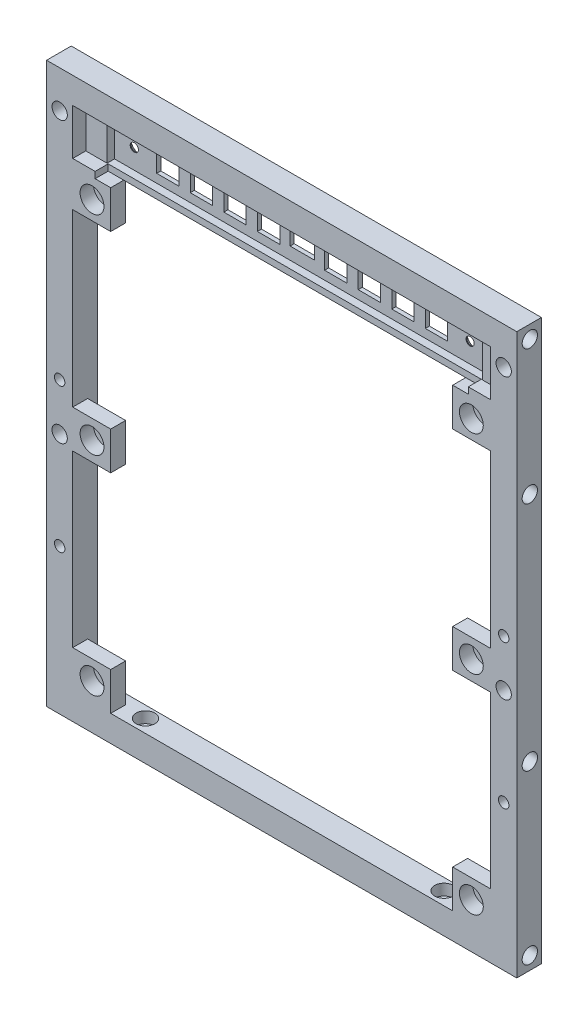
SolidWorks part; units mm, degrees
ref_plane "Front Plane" through (0, 0, 0) normal (0, 0, 1) x (1, 0, 0)
ref_plane "Top Plane" through (0, 0, 0) normal (0, 1, 0) x (1, 0, 0)
ref_plane "Right Plane" through (0, 0, 0) normal (1, 0, 0) x (0, 0, -1)
sketch "Sketch1" plane through (0, 0, 0) normal (0, 0, 1) x (1, 0, 0)
  line L1 (-63, -75) -> (63, -75)
  line L2 (-63, -75) -> (-63, 75)
  line L3 (-63, 75) -> (63, 75)
  line L4 (63, -75) -> (63, 75)
  line L5 (-63, -75) -> (63, 75) construction
  line L6 (-63, 75) -> (63, -75) construction
  line L7 (-56, -68) -> (56, -68)
  line L8 (-56, -68) -> (-56, 68)
  line L9 (-56, 68) -> (56, 68)
  line L10 (56, -68) -> (56, 68)
  line L11 (-56, -68) -> (56, 68) construction
  line L12 (-56, 68) -> (56, -68) construction
  point P0 (0, 0)
  point P6 (0, 0)
  dimension "D1" = 126
  dimension "D2" = 150
  dimension "D3" = 7
  dimension "D4" = 7
extrude "Boss-Extrude1" add sketch "Sketch1" along normal blind 7
sketch "Sketch2" plane through (-63, 0, 0) normal (-1, 0, 0) x (0, 0, 1)
  line L0 (3.5, 71.5) -> (3.5, -71.5) construction
  line L1 (7, 75) -> (0, 75) construction
  circle A0 centre (3.5, -71.5) radius 2.05
  circle A2 centre (3.5, 71.5) radius 2.05
  circle A3 centre (3.5, 35.5) radius 2.05
  circle A4 centre (3.5, -26.5) radius 2.05
  point P2 (3.5, 0)
  point P7 (3.5, 75)
  dimension "D2" = 4.1
  dimension "D3" = 36
  dimension "D4" = 45
  dimension "D1" = 3.5
extrude "Cut-Extrude1" cut sketch "Sketch2" against normal blind 6
mirror "Mirror1" about plane through (0, 0, 0) normal (1, 0, 0) of "Cut-Extrude1"
sketch "Sketch3" plane through (0, -68, 0) normal (0, 1, 0) x (1, 0, 0)
  line L0 (0, 0) -> (0, -7) construction
  line L1 (-56, 0) -> (56, 0) construction
  line L2 (-56, -7) -> (56, -7) construction
  line L3 (40, -3.5) -> (-40, -3.5) construction
  circle A0 centre (40, -3.5) radius 1.35
  circle A1 centre (-40, -3.5) radius 1.35
  point P9 (0, -3.5)
  dimension "D1" = 2.7
  dimension "D2" = 80
extrude "Cut-Extrude2" cut sketch "Sketch3" against normal through all
sketch "Sketch4" plane through (0, -68, 0) normal (0, 1, 0) x (1, 0, 0)
  circle A0 centre (40, -3.5) radius 2.5
  circle A1 centre (-40, -3.5) radius 2.5
  dimension "D1" = 5
extrude "Cut-Extrude3" cut sketch "Sketch4" against normal blind 3
sketch "Sketch5" plane through (0, 0, 0) normal (0, 0, -1) x (-1, 0, 0)
  line L0 (-59.5, -75) -> (-59.5, 75) construction
  line L1 (63, -75) -> (-63, -75) construction
  line L2 (-63, 75) -> (63, 75) construction
  line L3 (-56, 0) -> (-63, 0) construction
  line L4 (-56, -68) -> (-56, 68) construction
  line L5 (-63, -75) -> (-63, 75) construction
  line L6 (0, 75) -> (0, -75) construction
  line L7 (56, -68) -> (-56, -68) construction
  circle A0 centre (-59.5, 2.6) radius 1.4
  circle A1 centre (59.5, 2.6) radius 1.4
  circle A2 centre (-59.5, -36) radius 1.4
  circle A3 centre (59.5, -36) radius 1.4
  point P12 (-59.5, 0)
  point P13 (-59.5, 0)
  dimension "D1" = 2.8
  dimension "D2" = 2.6
  dimension "D3" = 32
extrude "Cut-Extrude4" cut sketch "Sketch5" against normal through all
sketch "Sketch6" plane through (0, 0, 0) normal (0, 0, -1) x (-1, 0, 0)
  circle A0 centre (-59.5, 2.6) radius 2.5
  circle A1 centre (59.5, 2.6) radius 2.5
  circle A2 centre (-59.5, -36) radius 2.5
  circle A3 centre (59.5, -36) radius 2.5
  dimension "D1" = 5
extrude "Cut-Extrude5" cut sketch "Sketch6" against normal blind 3
sketch "Sketch7" plane through (0, 0, 0) normal (0, 0, -1) x (-1, 0, 0)
  line L0 (-56, 68) -> (-63, 68) construction
  line L1 (-63, -75) -> (-63, 75) construction
  line L2 (-59.5, 65) -> (-59.5, -10) construction
  line L3 (-63, 75) -> (63, 75) construction
  circle A0 centre (-59.5, 65) radius 2.05
  circle A1 centre (-59.5, -10) radius 2.05
  point P8 (-59.5, 68)
  dimension "D1" = 4.1
  dimension "D2" = 10
  dimension "D3" = 75
extrude "Cut-Extrude6" cut sketch "Sketch7" against normal through all
mirror "Mirror2" about plane through (0, 0, 0) normal (1, 0, 0) of "Cut-Extrude6"
sketch "Sketch8" plane through (0, 0, 3) normal (0, 0, -1) x (-1, 0, 0)
  line L2 (-60.9, 0.5288) -> (-60.9, 4.6712)
  line L4 (-58.1, 0.5288) -> (-58.1, 4.6712)
  line L5 (-60.9, 0.5288) -> (-58.1, 4.6712) construction
  line L6 (-60.9, 4.6712) -> (-58.1, 0.5288) construction
  line L8 (-60.9, -38.0712) -> (-60.9, -33.9288)
  line L10 (-58.1, -38.0712) -> (-58.1, -33.9288)
  line L11 (-60.9, -38.0712) -> (-58.1, -33.9288) construction
  line L12 (-60.9, -33.9288) -> (-58.1, -38.0712) construction
  circle A0 centre (-59.5, 2.6) radius 2.5 construction
  circle A1 centre (-59.5, -36) radius 2.5 construction
  circle A2 centre (-59.5, -36) radius 2.5 construction
  arc A3 (-58.1, 4.6712) -> (-60.9, 4.6712) centre (-59.5, 2.6) ccw
  arc A4 (-58.1, -33.9288) -> (-60.9, -33.9288) centre (-59.5, -36) ccw
  circle A5 centre (-59.5, 2.6) radius 1.4 construction
  circle A6 centre (-59.5, -36) radius 1.4 construction
  arc A7 (-60.9, -38.0712) -> (-58.1, -38.0712) centre (-59.5, -36) ccw
  arc A8 (-60.9, 0.5288) -> (-58.1, 0.5288) centre (-59.5, 2.6) ccw
  point P0 (-59.5, 2.6)
  point P8 (-59.5, -36)
extrude "Cut-Extrude7" cut sketch "Sketch8" against normal blind 0.2
sketch "Sketch9" plane through (0, 0, 3.2) normal (0, 0, -1) x (-1, 0, 0)
  line L0 (-58.1, 2.6) -> (-58.1, 4.6712) construction
  line L1 (-60.9, 1.2) -> (-58.1, 1.2)
  line L2 (-60.9, 1.2) -> (-60.9, 4)
  line L3 (-60.9, 4) -> (-58.1, 4)
  line L4 (-58.1, 1.2) -> (-58.1, 4)
  line L5 (-60.9, 1.2) -> (-58.1, 4) construction
  line L6 (-60.9, 4) -> (-58.1, 1.2) construction
  line L7 (-58.1, -38.0712) -> (-58.1, -33.9288) construction
  line L8 (-60.9, -37.4) -> (-58.1, -37.4)
  line L9 (-60.9, -37.4) -> (-60.9, -34.6)
  line L10 (-60.9, -34.6) -> (-58.1, -34.6)
  line L11 (-58.1, -37.4) -> (-58.1, -34.6)
  line L12 (-60.9, -37.4) -> (-58.1, -34.6) construction
  line L13 (-60.9, -34.6) -> (-58.1, -37.4) construction
  arc A0 (-58.1, 2.6) -> (-60.9, 2.6) centre (-59.5, 2.6) ccw construction
  point P0 (-59.5, 2.6)
  point P8 (-59.5, -36)
extrude "Cut-Extrude8" cut sketch "Sketch9" against normal blind 0.2
mirror "Mirror3" about plane through (0, 0, 0) normal (1, 0, 0) of "Cut-Extrude8", "Cut-Extrude7"
sketch "Sketch10" plane through (0, 0, 7) normal (0, 0, 1) x (1, 0, 0)
  line L0 (56, -68) -> (56, 68) construction
  line L1 (56, -68) -> (50, -68)
  line L2 (56, -68) -> (56, -62)
  line L3 (56, -62) -> (50, -62)
  line L4 (50, -68) -> (50, -62)
  line L5 (56, -38.5) -> (50, -38.5)
  line L6 (56, -38.5) -> (56, -32.5)
  line L7 (56, -32.5) -> (50, -32.5)
  line L8 (50, -38.5) -> (50, -32.5)
  line L9 (-56, -68) -> (56, -68) construction
  dimension "D1" = 6
  dimension "D2" = 35.5
extrude "Boss-Extrude2" add sketch "Sketch10" against normal offset from surface (5.5 mm away) 1.5 up to face at (-57.45, -10, 0)
sketch "Sketch11" plane through (0, 0, 1.5) normal (0, 0, -1) x (-1, 0, 0)
  line L0 (-56, -38.5) -> (-50, -32.5) construction
  line L2 (-56, -68) -> (-50, -62) construction
  circle A0 centre (-53, -35.5) radius 1.65
  circle A1 centre (-53, -65) radius 1.65
  dimension "D1" = 3.3
extrude "Cut-Extrude9" cut sketch "Sketch11" against normal through all
mirror "Mirror4" about plane through (0, 0, 0) normal (1, 0, 0) of "Cut-Extrude9", "Boss-Extrude2"
sketch "Sketch12" plane through (0, 0, 0) normal (0, 0, -1) x (-1, 0, 0)
  line L0 (56, 68) -> (56, -68) construction
  line L1 (-56, 68) -> (56, 68)
  line L2 (-56, 68) -> (-56, 54)
  line L3 (-56, 54) -> (56, 54)
  line L4 (56, 68) -> (56, 54)
  dimension "D1" = 14
extrude "Boss-Extrude3" add sketch "Sketch12" against normal blind 1.5
sketch "Sketch13" plane through (0, 0, 1.5) normal (0, 0, 1) x (1, 0, 0)
  line L0 (-56, 68) -> (56, 54) construction
  line L2 (-50.3, 55.7) -> (50.3, 55.7)
  line L3 (-50.3, 55.7) -> (-50.3, 66.3)
  line L4 (-50.3, 66.3) -> (50.3, 66.3)
  line L5 (50.3, 55.7) -> (50.3, 66.3)
  line L6 (-50.3, 55.7) -> (50.3, 66.3) construction
  line L7 (-50.3, 66.3) -> (50.3, 55.7) construction
  line L8 (-56, 54) -> (56, 54)
  line L9 (-56, 54) -> (-56, 68)
  line L10 (-56, 68) -> (56, 68)
  line L11 (56, 54) -> (56, 68)
  line L12 (-56, 54) -> (56, 68) construction
  line L13 (-56, 68) -> (56, 54) construction
  point P4 (0, 61)
  point P9 (0, 61)
  dimension "D1" = 100.6
  dimension "D2" = 10.6
extrude "Boss-Extrude4" add sketch "Sketch13" along normal blind 2
sketch "Sketch14" plane through (0, 0, 1.5) normal (0, 0, 1) x (1, 0, 0)
  line L0 (0, 66.3) -> (0, 55.7) construction
  line L1 (50.3, 66.3) -> (-50.3, 66.3) construction
  line L2 (-50.3, 55.7) -> (50.3, 55.7) construction
  line L3 (-50.3, 61) -> (50.3, 61) construction
  line L4 (50.3, 55.7) -> (50.3, 66.3) construction
  line L5 (-33, 64) -> (-39, 64)
  line L6 (-3.25, 59) -> (3.25, 59)
  line L7 (-3.25, 59) -> (-3.25, 63)
  line L8 (-3.25, 63) -> (3.25, 63)
  line L9 (3.25, 59) -> (3.25, 63)
  line L10 (-3.25, 59) -> (3.25, 63) construction
  line L11 (-3.25, 63) -> (3.25, 59) construction
  line L12 (6, 58) -> (12, 58)
  line L13 (6, 58) -> (6, 64)
  line L14 (6, 64) -> (12, 64)
  line L15 (12, 58) -> (12, 64)
  line L16 (6, 58) -> (12, 64) construction
  line L17 (6, 64) -> (12, 58) construction
  line L18 (15, 58) -> (21, 58)
  line L19 (15, 58) -> (15, 64)
  line L20 (15, 64) -> (21, 64)
  line L21 (21, 58) -> (21, 64)
  line L22 (15, 58) -> (21, 64) construction
  line L23 (15, 64) -> (21, 58) construction
  line L24 (24, 58) -> (30, 58)
  line L25 (24, 58) -> (24, 64)
  line L26 (24, 64) -> (30, 64)
  line L27 (30, 58) -> (30, 64)
  line L28 (24, 58) -> (30, 64) construction
  line L29 (24, 64) -> (30, 58) construction
  line L30 (33, 58) -> (39, 58)
  line L31 (33, 58) -> (33, 64)
  line L32 (33, 64) -> (39, 64)
  line L33 (39, 58) -> (39, 64)
  line L34 (33, 58) -> (39, 64) construction
  line L35 (33, 64) -> (39, 58) construction
  line L36 (-39, 58) -> (-39, 64)
  line L37 (-33, 58) -> (-39, 58)
  line L38 (-33, 58) -> (-33, 64)
  line L39 (-24, 64) -> (-30, 64)
  line L40 (-30, 58) -> (-30, 64)
  line L41 (-24, 58) -> (-30, 58)
  line L42 (-24, 58) -> (-24, 64)
  line L43 (-15, 64) -> (-21, 64)
  line L44 (-21, 58) -> (-21, 64)
  line L45 (-15, 58) -> (-21, 58)
  line L46 (-15, 58) -> (-15, 64)
  line L47 (-6, 64) -> (-12, 64)
  line L48 (-12, 58) -> (-12, 64)
  line L49 (-6, 58) -> (-12, 58)
  line L50 (-6, 58) -> (-6, 64)
  circle A0 centre (-45, 61) radius 1.3 construction
  circle A1 centre (45, 61) radius 1.3 construction
  point P6 (0, 61)
  point P11 (0, 61)
  point P16 (9, 61)
  point P21 (18, 61)
  point P26 (27, 61)
  point P31 (36, 61)
  dimension "D10" = 2.6
  dimension "D9" = 45
  dimension "D1" = 6.5
  dimension "D2" = 4
  dimension "D3" = 6
  dimension "D4" = 9
  dimension "D5" = 9
  dimension "D6" = 9
  dimension "D7" = 9
  dimension "D8" = 45
extrude "Cut-Extrude10" cut sketch "Sketch14" against normal through all
sketch "Sketch15" plane through (0, 0, 1.5) normal (0, 0, 1) x (1, 0, 0)
  circle A0 centre (-45, 61) radius 1
  circle A1 centre (45, 61) radius 1
  dimension "D1" = 2
extrude "Boss-Extrude5" add sketch "Sketch15" along normal up to surface (2 mm away) up to face at (0, 61, 3.5)
chamfer "Chamfer1" distance 0.4 angle 45 3 edges at (-56, -7, 0) (56, -7, 0) (0, -68, 0) tangent propagation no
chamfer "Chamfer2" distance 0.4 angle 45 4 edges at (0, 75, 0) (-63, 0, 0) (0, -75, 0) (63, 0, 0)
chamfer "Chamfer3" distance 0.4 angle 45 36 edges at (-36, 58, 0) (-39, 61, 0) (-36, 64, 0) (-33, 61, 0) (-27, 58, 0) (-30, 61, 0) (-27, 64, 0) (-24, 61, 0) (-18, 58, 0) (-21, 61, 0) (-18, 64, 0) (-15, 61, 0) (-9, 58, 0) (-12, 61, 0) (-9, 64, 0) (-6, 61, 0) (0, 59, 0) (-3.25, 61, 0) (0, 63, 0) (3.25, 61, 0) (9, 58, 0) (6, 61, 0) (9, 64, 0) (12, 61, 0) (18, 58, 0) (15, 61, 0) (18, 64, 0) (21, 61, 0) (36, 58, 0) (33, 61, 0) (36, 64, 0) (39, 61, 0) (27, 58, 0) (24, 61, 0) (27, 64, 0) (30, 61, 0)
sketch "Sketch16" plane through (0, 0, 7) normal (0, 0, 1) x (1, 0, 0)
  line L0 (-50, 54) -> (-50, 55.7)
  line L1 (-56, -32.5) -> (-50, -32.5)
  line L2 (-56, -32.5) -> (-56, -26.5)
  line L3 (-56, -26.5) -> (-50, -26.5)
  line L4 (-50, -32.5) -> (-50, -26.5)
  line L5 (56, -32.5) -> (50, -32.5)
  line L6 (56, -32.5) -> (56, -26.5)
  line L7 (56, -26.5) -> (50, -26.5)
  line L8 (50, -32.5) -> (50, -26.5)
  line L9 (56, 54) -> (50, 54) construction
  line L10 (56, 54) -> (56, 48)
  line L11 (56, 48) -> (50, 48)
  line L12 (50, 54) -> (50, 48)
  line L13 (-56, 54) -> (-50, 54) construction
  line L14 (-56, 54) -> (-56, 48)
  line L15 (-56, 48) -> (-50, 48)
  line L16 (-50, 54) -> (-50, 48)
  line L17 (-50.3, 55.7) -> (50.3, 55.7) construction
  line L18 (-50, 55.7) -> (-56, 55.7)
  line L19 (-56, 68) -> (-56, 54) construction
  line L20 (-56, 55.7) -> (-56, 54)
  line L21 (50, 54) -> (50, 55.7)
  line L22 (50, 55.7) -> (56, 55.7)
  line L23 (56, 54) -> (56, 68) construction
  line L24 (56, 55.7) -> (56, 54)
  dimension "D1" = 6
extrude "Boss-Extrude7" add sketch "Sketch16" against normal offset from surface (5.5 mm away) 1.5 up to face at (-36, 61, 0)
sketch "Sketch17" plane through (0, 0, 1.5) normal (0, 0, -1) x (-1, 0, 0)
  line L0 (-50, 48) -> (50, -26.5) construction
  line L1 (-50, -26.5) -> (-50, -38.5) construction
  line L2 (-53, -29.5) -> (53, -29.5) construction
  line L3 (-53, -29.5) -> (-53, 51) construction
  line L4 (-53, 51) -> (53, 51) construction
  line L5 (53, -29.5) -> (53, 51) construction
  line L6 (-53, -29.5) -> (53, 51) construction
  line L7 (-53, 51) -> (53, -29.5) construction
  line L8 (50, -26.5) -> (56, -26.5) construction
  circle A0 centre (-53, -29.5) radius 1.65
  circle A1 centre (53, -29.5) radius 1.65
  circle A2 centre (53, 51) radius 1.65
  circle A3 centre (-53, 51) radius 1.65
  point P4 (0, 10.75)
  dimension "D3" = 3.3
  dimension "D1" = 3
  dimension "D2" = 3
extrude "Cut-Extrude11" cut sketch "Sketch17" against normal through all
sketch "Sketch18" plane through (0, 0, 1.5) normal (0, 0, 1) x (1, 0, 0)
  circle A0 centre (-45, 61) radius 1.1
  circle A1 centre (45, 61) radius 1.1
  dimension "D1" = 2.2
extrude "Cut-Extrude12" cut sketch "Sketch18" against normal through all both and the other way through all
chamfer "Chamfer4" distance 1.3 angle 45 2 edges at (-43.9, 61, 0) (46.1, 61, 0)
sketch "Sketch19" plane through (0, 0, 1.5) normal (0, 0, -1) x (-1, 0, 0)
  line L1 (-56, -68) -> (56, -68)
  line L2 (-56, -68) -> (-56, 54)
  line L3 (-56, 54) -> (56, 54)
  line L4 (56, -68) -> (56, 54)
extrude "Cut-Extrude13" cut sketch "Sketch19" against normal through all
ref_plane "Plane1" through (0, 0, 3) normal (0, 0, 1) x (1, 0, 0)
sketch "Sketch20" plane through (0, 0, 3) normal (0, 0, 1) x (1, 0, 0)
  line L0 (56, 54) -> (56, -68) construction
  line L1 (56, -68) -> (48, -68)
  line L2 (56, -68) -> (56, -60)
  line L3 (56, -60) -> (48, -60)
  line L4 (48, -68) -> (48, -60)
  line L5 (56, 54) -> (48, 54)
  line L6 (56, 54) -> (56, 46)
  line L7 (56, 46) -> (48, 46)
  line L8 (48, 54) -> (48, 46)
  line L9 (56, -24.5) -> (48, -24.5)
  line L10 (56, -24.5) -> (56, -32.5)
  line L11 (56, -32.5) -> (48, -32.5)
  line L12 (48, -24.5) -> (48, -32.5)
  dimension "D1" = 8
  dimension "D2" = 27.5
extrude "Boss-Extrude8" add sketch "Sketch20" along normal blind 7
sketch "Sketch21" plane through (0, 0, 3) normal (0, 0, -1) x (-1, 0, 0)
  line L0 (-48, 54) -> (-56, 46) construction
  line L1 (-56, -60) -> (-48, -68) construction
  line L2 (-56, -24.5) -> (-48, -32.5) construction
  circle A0 centre (-52, 50) radius 2.1
  circle A1 centre (-52, -64) radius 2.1
  circle A2 centre (-52, -28.5) radius 2.1
  dimension "D1" = 4.2
extrude "Cut-Extrude14" cut sketch "Sketch21" against normal through all
mirror "Mirror5" about plane through (0, 0, 0) normal (1, 0, 0) of "Cut-Extrude14", "Boss-Extrude8"
chamfer "Chamfer5" distance 3 angle 45 6 edges at (-56, -64, 7) (56, -64, 7) (56, 50, 7) (-56, 50, 7) (-56, -28.5, 7) (56, -28.5, 7)
sketch "Sketch22" plane through (0, 0, 3) normal (0, 0, -1) x (-1, 0, 0)
  line L1 (-56, 54) -> (56, 54)
  line L2 (-56, 54) -> (-56, -68)
  line L3 (-56, -68) -> (56, -68)
  line L4 (56, 54) -> (56, -68)
extrude "Cut-Extrude15" cut sketch "Sketch22" against normal blind 10
sketch "Sketch23" plane through (-56, 0, 0) normal (1, 0, 0) x (0, 0, -1)
  line L1 (-7, 54) -> (-10, 54)
  line L2 (-7, 54) -> (-7, -68)
  line L3 (-7, -68) -> (-10, -68)
  line L4 (-10, 54) -> (-10, -68)
extrude "Cut-Extrude16" cut sketch "Sketch23" against normal through all both and the other way through all
sketch "Sketch24" plane through (0, 0, 0) normal (0, 0, -1) x (-1, 0, 0)
  circle A0 centre (-50.825, 48.75) radius 3.2 construction
  circle A1 centre (-50.825, -62.95) radius 3.2 construction
  circle A2 centre (-50.825, -7.1) radius 3.2 construction
  circle A3 centre (50.825, -62.95) radius 3.2 construction
  circle A4 centre (50.825, -7.1) radius 3.2 construction
  circle A5 centre (50.825, 48.75) radius 3.2 construction
  circle A6 centre (-50.825, 48.75) radius 3.2
  circle A7 centre (-50.825, -62.95) radius 3.2
  circle A8 centre (-50.825, -7.1) radius 3.2
  circle A9 centre (50.825, -62.95) radius 3.2
  circle A10 centre (50.825, -7.1) radius 3.2
  circle A11 centre (50.825, 48.75) radius 3.2
sketch "Sketch25" plane through (0, 0, 3) normal (0, 0, 1) x (1, 0, 0)
  line L0 (-56, 54) -> (-56, -68) construction
  line L1 (-56, 54) -> (-45.825, 54)
  line L2 (-56, 54) -> (-56, 43.825)
  line L3 (-56, 43.825) -> (-45.825, 43.825)
  line L4 (-45.825, 54) -> (-45.825, 43.825)
  line L5 (-56, -2.0125) -> (-45.825, -2.0125)
  line L6 (-56, -2.0125) -> (-56, -12.1875)
  line L7 (-56, -12.1875) -> (-45.825, -12.1875)
  line L8 (-45.825, -2.0125) -> (-45.825, -12.1875)
  line L9 (0, 54) -> (0, -68) construction
  line L10 (-56, -68) -> (-45.825, -68)
  line L11 (-56, -68) -> (-56, -57.825)
  line L12 (-56, -57.825) -> (-45.825, -57.825)
  line L13 (-45.825, -68) -> (-45.825, -57.825)
  line L14 (-50, 54) -> (50, 54) construction
  line L15 (-56, -68) -> (56, -68) construction
  line L16 (45.825, -68) -> (45.825, -57.825)
  line L17 (56, -57.825) -> (45.825, -57.825)
  line L18 (56, -68) -> (56, -57.825)
  line L19 (56, -68) -> (45.825, -68)
  line L20 (45.825, -2.0125) -> (45.825, -12.1875)
  line L21 (56, -12.1875) -> (45.825, -12.1875)
  line L22 (56, -2.0125) -> (56, -12.1875)
  line L23 (56, -2.0125) -> (45.825, -2.0125)
  line L24 (45.825, 54) -> (45.825, 43.825)
  line L25 (56, 43.825) -> (45.825, 43.825)
  line L26 (56, 54) -> (56, 43.825)
  line L27 (56, 54) -> (45.825, 54)
  point P16 (-45.825, -7.1)
  dimension "D1" = 5
extrude "Boss-Extrude9" add sketch "Sketch25" along normal up to surface (4 mm away) up to face at (0, 0, 7)
sketch "Sketch26" plane through (0, 0, 7) normal (0, 0, 1) x (1, 0, 0)
  circle A0 centre (-50.825, -7.1) radius 3.2 construction
  circle A1 centre (-50.825, -62.95) radius 3.2 construction
  circle A2 centre (50.825, -62.95) radius 3.2 construction
  circle A3 centre (50.825, -7.1) radius 3.2 construction
  circle A4 centre (50.825, 48.75) radius 3.2 construction
  circle A5 centre (-50.825, 48.75) radius 3.2 construction
  circle A6 centre (-50.825, -7.1) radius 3.2
  circle A7 centre (-50.825, -62.95) radius 3.2
  circle A8 centre (50.825, -62.95) radius 3.2
  circle A9 centre (50.825, -7.1) radius 3.2
  circle A10 centre (50.825, 48.75) radius 3.2
  circle A11 centre (-50.825, 48.75) radius 3.2
extrude "Cut-Extrude17" cut sketch "Sketch26" against normal offset from surface (3.6 mm away) 0.4 up to face at (-50.9125, 48.9125, 3)
